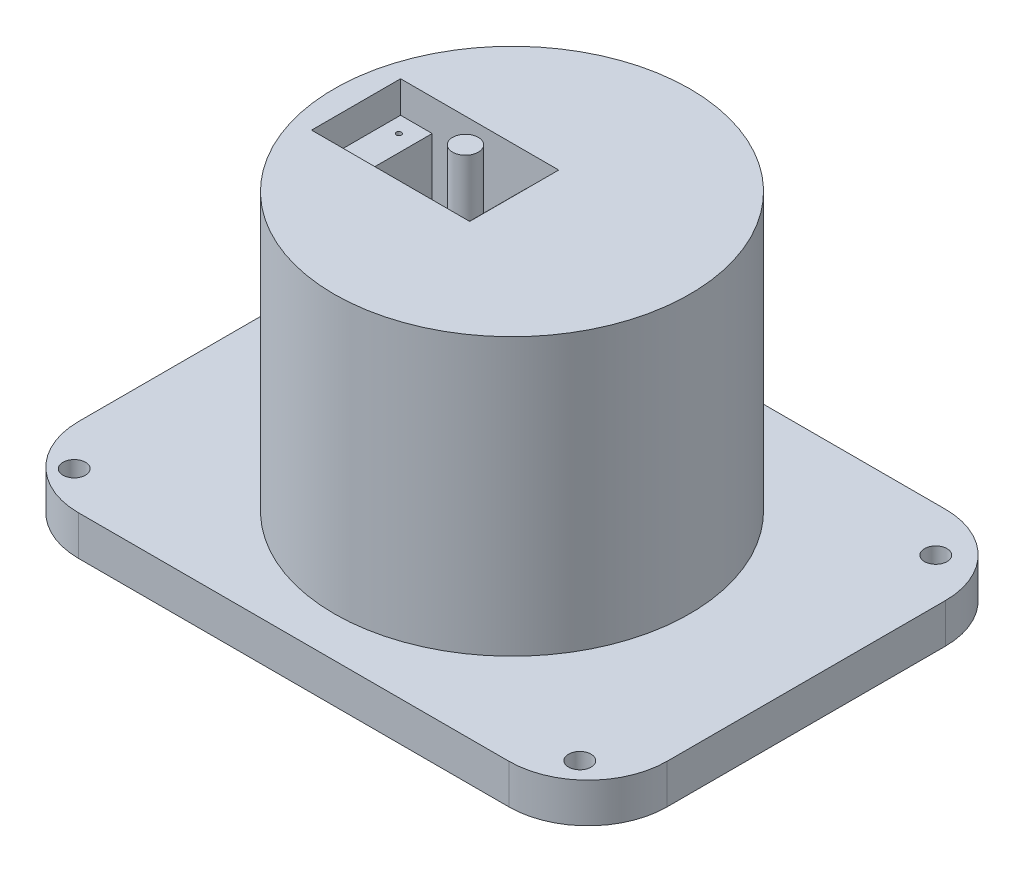
SolidWorks part; units mm, degrees
ref_plane "Front Plane" through (0, 0, 0) normal (0, 0, 1) x (1, 0, 0)
ref_plane "Top Plane" through (0, 0, 0) normal (0, 1, 0) x (1, 0, 0)
ref_plane "Right Plane" through (0, 0, 0) normal (1, 0, 0) x (0, 0, -1)
sketch "Sketch2" plane through (0, 0, 0) normal (0, 1, 0) x (1, 0, 0)
  line L1 (-54.4356, 55.2127) -> (54.4356, 55.2127)
  line L2 (-74.4356, 35.2127) -> (-74.4356, -35.2127)
  line L3 (-54.4356, -55.2127) -> (54.4356, -55.2127)
  line L4 (74.4356, 35.2127) -> (74.4356, -35.2127)
  line L5 (-74.4356, 55.2127) -> (74.4356, -55.2127) construction
  line L6 (-74.4356, -55.2127) -> (74.4356, 55.2127) construction
  arc A1 (54.4356, -55.2127) -> (74.4356, -35.2127) centre (54.4356, -35.2127) ccw
  arc A2 (-74.4356, -35.2127) -> (-54.4356, -55.2127) centre (-54.4356, -35.2127) ccw
  arc A3 (54.4356, 55.2127) -> (74.4356, 35.2127) centre (54.4356, 35.2127) cw
  arc A4 (-54.4356, 55.2127) -> (-74.4356, 35.2127) centre (-54.4356, 35.2127) ccw
  dimension "D1" = 20
extrude "Boss-Extrude2" add sketch "Sketch2" along normal blind 10
sketch "Sketch3" plane through (0, 10, 0) normal (0, 1, 0) x (1, 0, 0)
  circle A0 centre (0, 0) radius 45
  dimension "D1" = 90
extrude "Boss-Extrude3" add sketch "Sketch3" along normal blind 70
sketch "Sketch5" plane through (0, 80, 0) normal (0, 1, 0) x (1, 0, 0)
  line L1 (-38.7959, 10.6102) -> (1.2041, 10.6102)
  line L2 (-38.7959, 10.6102) -> (-38.7959, -11.9061)
  line L3 (-38.7959, -11.9061) -> (1.2041, -11.9061)
  line L4 (1.2041, 10.6102) -> (1.2041, -11.9061)
  dimension "D1" = 40
  dimension "D2" = 22.5162
extrude "Cut-Extrude1" cut sketch "Sketch5" against normal blind 40
sketch "Sketch6" plane through (0, 40, 0) normal (0, 1, 0) x (1, 0, 0)
  line L0 (-38.7959, -11.9061) -> (1.2041, -11.9061) construction
  line L1 (-38.7959, 10.6102) -> (-30.7947, 10.6102)
  line L2 (-38.7959, 10.6102) -> (-38.7959, -11.9061)
  line L3 (-38.7959, -11.9061) -> (-30.7947, -11.9061)
  line L4 (-30.7947, 10.6102) -> (-30.7947, -11.9061)
  line L5 (-38.7959, -11.9061) -> (1.2041, -11.9061) construction
  line L6 (1.2041, 10.6102) -> (-6.8377, 10.6102)
  line L7 (1.2041, 10.6102) -> (1.2041, -11.9061)
  line L8 (1.2041, -11.9061) -> (-6.8377, -11.9061)
  line L9 (-6.8377, 10.6102) -> (-6.8377, -11.9061)
extrude "Boss-Extrude4" add sketch "Sketch6" along normal blind 32
sketch "Sketch8" plane through (0, 72, 0) normal (0, 1, 0) x (1, 0, 0)
  line L0 (-38.7959, -0.6479) -> (1.2041, -0.6479) construction
  line L1 (-38.7959, 10.6102) -> (-38.7959, -11.9061) construction
  line L2 (1.2041, -11.9061) -> (1.2041, 10.6102) construction
  circle A0 centre (-3.1503, 6.3734) radius 0.6569
  circle A1 centre (-3.1503, -7.0899) radius 0.65
  circle A2 centre (-34.9902, 6.3734) radius 0.65
  circle A3 centre (-34.9902, -7.0899) radius 0.65
  dimension "D1" = 1.3139
  dimension "D2" = 1.3
  dimension "D3" = 1.3
  dimension "D4" = 1.3
extrude "Cut-Extrude2" cut sketch "Sketch8" against normal blind 6
shell "Shell16" thickness 10 removed face at (0, 10, 45)
sketch "Sketch9" plane through (0, 10, 0) normal (0, 1, 0) x (1, 0, 0)
  line L0 (-64.6364, 43.9386) -> (-64.6364, -46.1063) construction
  line L1 (-64.6364, 43.9386) -> (63.2608, 43.9386) construction
  line L2 (63.2608, 43.9386) -> (63.2608, -46.1063) construction
  line L3 (63.2608, -46.1063) -> (-64.6364, -46.1063) construction
  circle A0 centre (-64.6364, 43.9386) radius 2.85
  circle A1 centre (63.2608, 43.9386) radius 2.85
  circle A2 centre (-64.6364, -46.1063) radius 2.85
  circle A3 centre (63.2608, -46.1063) radius 2.85
  dimension "D1" = 5.7
  dimension "D2" = 5.7
  dimension "D3" = 5.7
  dimension "D4" = 5.7
extrude "Cut-Extrude3" cut sketch "Sketch9" against normal blind 6
sketch "Sketch10" plane through (0, 40, 0) normal (0, 1, 0) x (1, 0, 0)
  line L0 (-30.7947, -0.6479) -> (-6.8377, -0.6479) construction
  line L1 (-30.7947, -11.9061) -> (-30.7947, 10.6102) construction
  line L2 (-6.8377, 10.6102) -> (-6.8377, -11.9061) construction
  circle A0 centre (-11.1276, -0.6479) radius 3.25
  dimension "D1" = 6.5
extrude "Boss-Extrude5" add sketch "Sketch10" along normal blind 45
